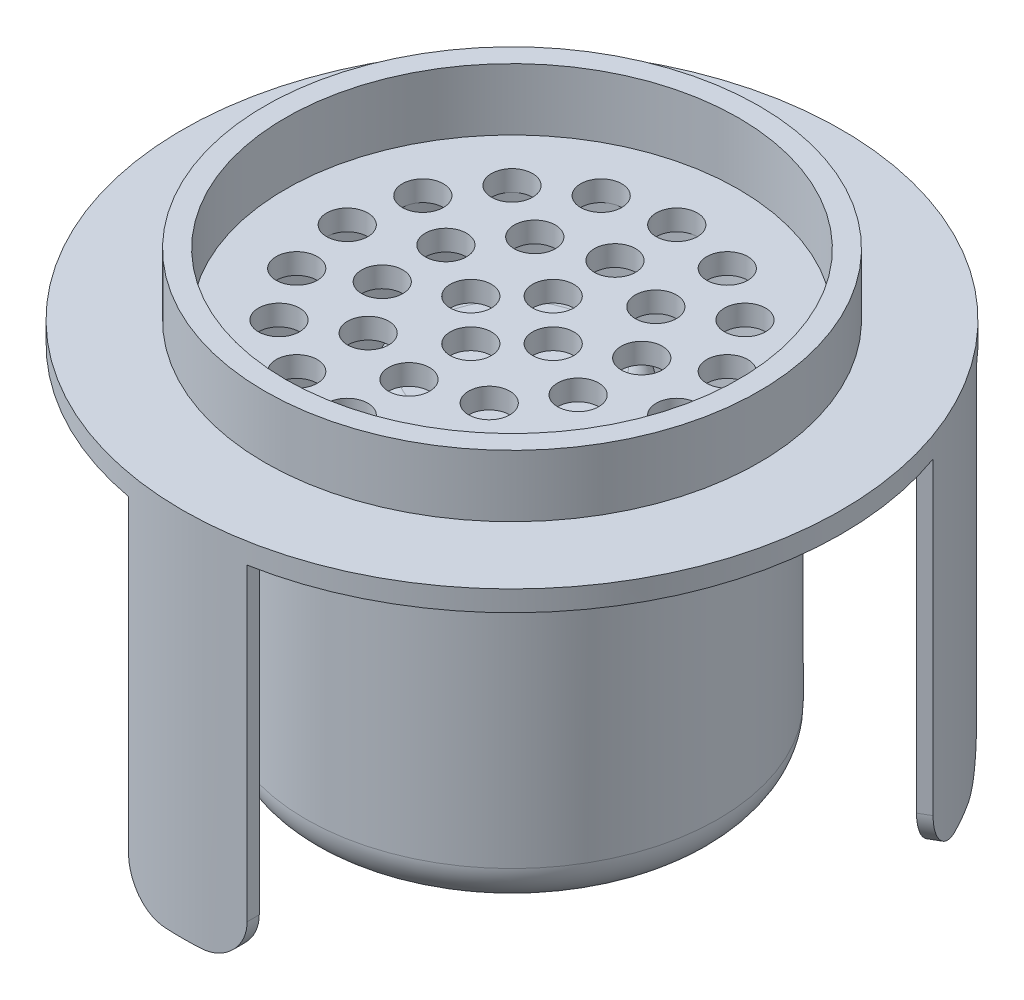
SolidWorks part; units mm, degrees
ref_plane "Front Plane" through (0, 0, 0) normal (0, 0, 1) x (1, 0, 0)
ref_plane "Top Plane" through (0, 0, 0) normal (0, 1, 0) x (1, 0, 0)
ref_plane "Right Plane" through (0, 0, 0) normal (1, 0, 0) x (0, 0, -1)
sketch "Sketch1" plane through (0, 0, 0) normal (0, 0, 1) x (1, 0, 0)
  line L0 (0, 16.5844) -> (0, -16.9581) construction
  line L1 (16, 0) -> (16, 12.2892)
  line L2 (16, 0) -> (12, 0)
  line L3 (11, 0) -> (11, 1)
  line L4 (12, 1) -> (16, 1)
  line L5 (11, 1) -> (11, 4)
  line L6 (11, 4) -> (12, 4)
  line L7 (12, 4) -> (12, 1)
  line L8 (10, -4) -> (10, -17)
  line L9 (11, 0) -> (9, 0)
  line L10 (11, -1) -> (11, -4)
  line L11 (11, -4) -> (10, -4)
  line L12 (9, 0) -> (9, -4)
  line L13 (10, -17) -> (4, -17)
  line L14 (4, -17) -> (4, -2)
  line L16 (9, -4) -> (9, -16)
  line L17 (5, -1) -> (5, -16)
  line L18 (5, -16) -> (9, -16)
  line L22 (4, -2) -> (0, -2)
  line L23 (0, -2) -> (0, -1)
  line L24 (0, -1) -> (5, -1)
  arc A0 (11, -1) -> (12, 0) centre (11, 0) ccw
  dimension "D1" = 15
  dimension "D2" = 5
  dimension "D3" = 15
  dimension "D7" = 21
revolve "Revolve2" add sketch "Sketch1" angle 360 about L0
fillet "Fillet1" radius 1 3 edges at (0, -4, 11) (0, -2, 4) (0, -1, 5)
fillet "Fillet2" radius 2 4 edges at (0, -17, 10) (0, -17, 4) (0, -16, 5) (0, -16, 9)
sketch "Sketch2" plane through (0, 1, 0) normal (0, 1, 0) x (1, 0, 0)
  line L13 (-2.8775, -15.1492) -> (-2.8775, -15.7391)
  line L17 (2.8775, -15.1492) -> (2.8775, -15.7391)
  line L18 (-2.8775, -15.1492) -> (0, -16) construction
  line L19 (0, -16) -> (2.8775, -15.1492) construction
  circle A11 centre (0, 0) radius 16 construction
  arc A15 (-2.8775, -15.7391) -> (2.8775, -15.7391) centre (0, 0) ccw
  arc A16 (-2.8775, -15.1492) -> (2.8775, -15.1492) centre (0, 0) ccw
  point P0 (0, -16)
  point P16 (0, 0)
  point P21 (0, 0)
extrude "Boss-Extrude3" add sketch "Sketch2" against normal blind 18
ref_plane "Plane2" through (0, 0, -10) normal (0, 0, 1) x (1, 0, 0)
sketch "Sketch11" plane through (0, 0, 0) normal (0, 1, 0) x (1, 0, 0)
  circle A0 centre (0, 0) radius 11
  circle A1 centre (0, -2) radius 1
  circle A2 centre (0, -5) radius 1
  circle A3 centre (0, -8) radius 1
  circle A5 centre (-2, 0) radius 1
  circle A6 centre (0, 2) radius 1
  circle A7 centre (2, 0) radius 1
  circle A9 centre (-2.9389, -4.0451) radius 1
  circle A10 centre (-4.7553, -1.5451) radius 1
  circle A11 centre (-4.7553, 1.5451) radius 1
  circle A12 centre (-2.9389, 4.0451) radius 1
  circle A13 centre (0, 5) radius 1
  circle A14 centre (2.9389, 4.0451) radius 1
  circle A15 centre (4.7553, 1.5451) radius 1
  circle A16 centre (4.7553, -1.5451) radius 1
  circle A17 centre (2.9389, -4.0451) radius 1
  circle A18 centre (-3.0615, -7.391) radius 1
  circle A19 centre (-5.6569, -5.6569) radius 1
  circle A20 centre (-7.391, -3.0615) radius 1
  circle A21 centre (-8, 0) radius 1
  circle A22 centre (-7.391, 3.0615) radius 1
  circle A23 centre (-5.6569, 5.6569) radius 1
  circle A24 centre (-3.0615, 7.391) radius 1
  circle A25 centre (0, 8) radius 1
  circle A26 centre (3.0615, 7.391) radius 1
  circle A27 centre (5.6569, 5.6569) radius 1
  circle A28 centre (7.391, 3.0615) radius 1
  circle A29 centre (8, 0) radius 1
  circle A30 centre (7.391, -3.0615) radius 1
  circle A31 centre (5.6569, -5.6569) radius 1
  circle A32 centre (3.0615, -7.391) radius 1
  point P18 (0, 0)
  point P37 (0, 0)
  point P68 (0, 0)
  dimension "D1" = 2
  dimension "D2" = 3
  dimension "D3" = 3
  dimension "D4" = 4
  dimension "D5" = 10
  dimension "D6" = 16
extrude "Boss-Extrude4" add sketch "Sketch11" along normal blind 1
pattern_circular "CirPattern1" count 3 over 360 about axis through (0, 0, 0) along (0, 1, 0) of "Boss-Extrude3"
fillet "Fillet3" radius 2 6 edges at (-2.8775, -17, 15.4441) (2.8775, -17, 15.4441) (-14.8138, -17, -5.2301) (-11.9363, -17, -10.2141) (11.9363, -17, -10.2141) (14.8138, -17, -5.2301)
